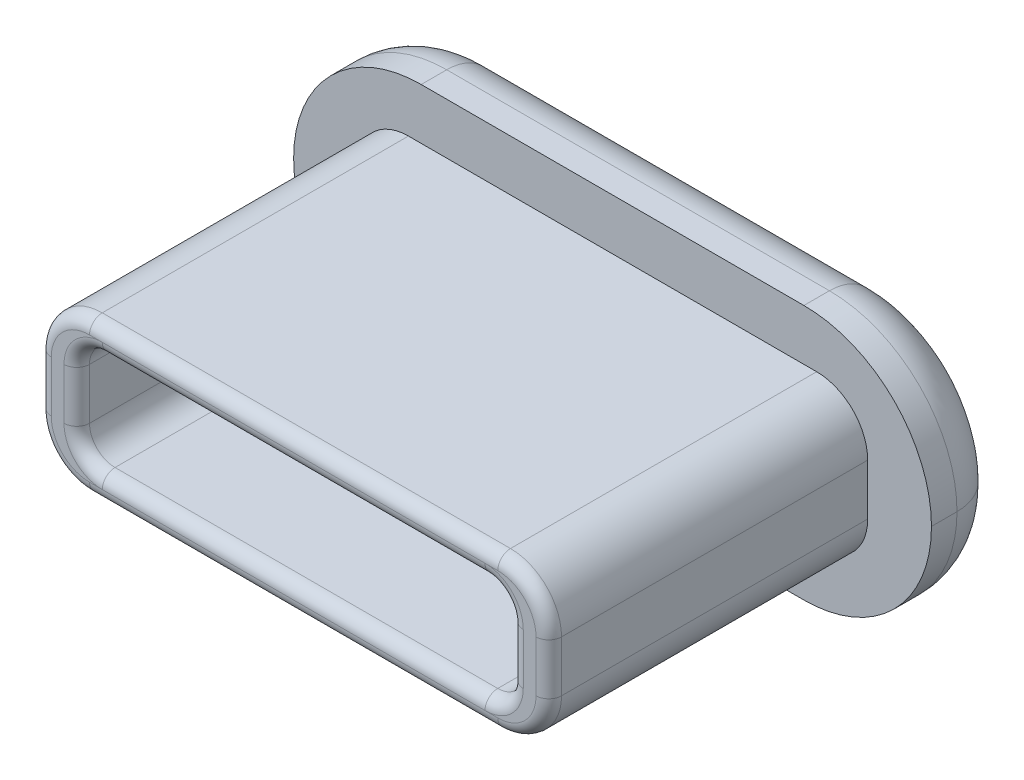
SolidWorks part; units mm, degrees
ref_plane "Спереди" through (0, 0, 0) normal (0, 0, 1) x (1, 0, 0)
ref_plane "Сверху" through (0, 0, 0) normal (0, 1, 0) x (1, 0, 0)
ref_plane "Справа" through (0, 0, 0) normal (1, 0, 0) x (0, 0, -1)
other "Configuration Table"
sketch "Эскиз1" plane through (0, 0, 0) normal (0, 0, 1) x (1, 0, 0)
  line L1 (-5, 2) -> (5, 2)
  line L2 (-5, 2) -> (-5, -2)
  line L3 (-5, -2) -> (5, -2)
  line L4 (5, 2) -> (5, -2)
  line L5 (-5, 2) -> (5, -2) construction
  line L6 (-5, -2) -> (5, 2) construction
  point P0 (0, 0)
  dimension "D1" = 10
  dimension "D2" = 4
extrude "Бобышка-Вытянуть1" add sketch "Эскиз1" along normal blind 1.2
sketch "Эскиз2" plane through (0, 0, 1.2) normal (0, 0, 1) x (1, 0, 0)
  line L1 (-4, 1.2) -> (4, 1.2)
  line L2 (-4, 1.2) -> (-4, -1.2)
  line L3 (-4, -1.2) -> (4, -1.2)
  line L4 (4, 1.2) -> (4, -1.2)
  line L5 (-4, 1.2) -> (4, -1.2) construction
  line L6 (-4, -1.2) -> (4, 1.2) construction
  line L7 (-3.4, 0.8) -> (3.4, 0.8)
  line L8 (-3.4, 0.8) -> (-3.4, -0.8)
  line L9 (-3.4, -0.8) -> (3.4, -0.8)
  line L10 (3.4, 0.8) -> (3.4, -0.8)
  line L11 (-3.4, 0.8) -> (3.4, -0.8) construction
  line L12 (-3.4, -0.8) -> (3.4, 0.8) construction
  point P0 (0, 0)
  point P6 (0, 0)
  dimension "D1" = 8
  dimension "D2" = 2.4
  dimension "D3" = 1.6
  dimension "D4" = 6.8
extrude "Бобышка-Вытянуть2" add sketch "Эскиз2" along normal blind 5
fillet "Скругление1" radius 2 4 edges at (5, 2, 0.6) (5, -2, 0.6) (-5, -2, 0.6) (-5, 2, 0.6)
fillet "Скругление2" radius 0.8 6 edges at (-4.4142, 1.4142, 0) (-4.4142, -1.4142, 0) (0, -2, 0) (4.4142, -1.4142, 0) (4.4142, 1.4142, 0) (0, 2, 0)
fillet "Скругление3" radius 0.8 4 edges at (-4, -1.2, 3.7) (4, -1.2, 3.7) (4, 1.2, 3.7) (-4, 1.2, 3.7)
fillet "Скругление4" radius 0.4 4 edges at (-3.4, 0.8, 3.7) (-3.4, -0.8, 3.7) (3.4, -0.8, 3.7) (3.4, 0.8, 3.7)
fillet "Скругление5" radius 0.2 16 edges at (-3.2828, 0.6828, 6.2) (-3.4, 0, 6.2) (-3.2828, -0.6828, 6.2) (0, -0.8, 6.2) (3.2828, -0.6828, 6.2) (3.4, 0, 6.2) (3.2828, 0.6828, 6.2) (0, 0.8, 6.2) (-3.7657, 0.9657, 6.2) (0, 1.2, 6.2) (3.7657, 0.9657, 6.2) (4, 0, 6.2) (3.7657, -0.9657, 6.2) (0, -1.2, 6.2) (-3.7657, -0.9657, 6.2) (-4, 0, 6.2)
